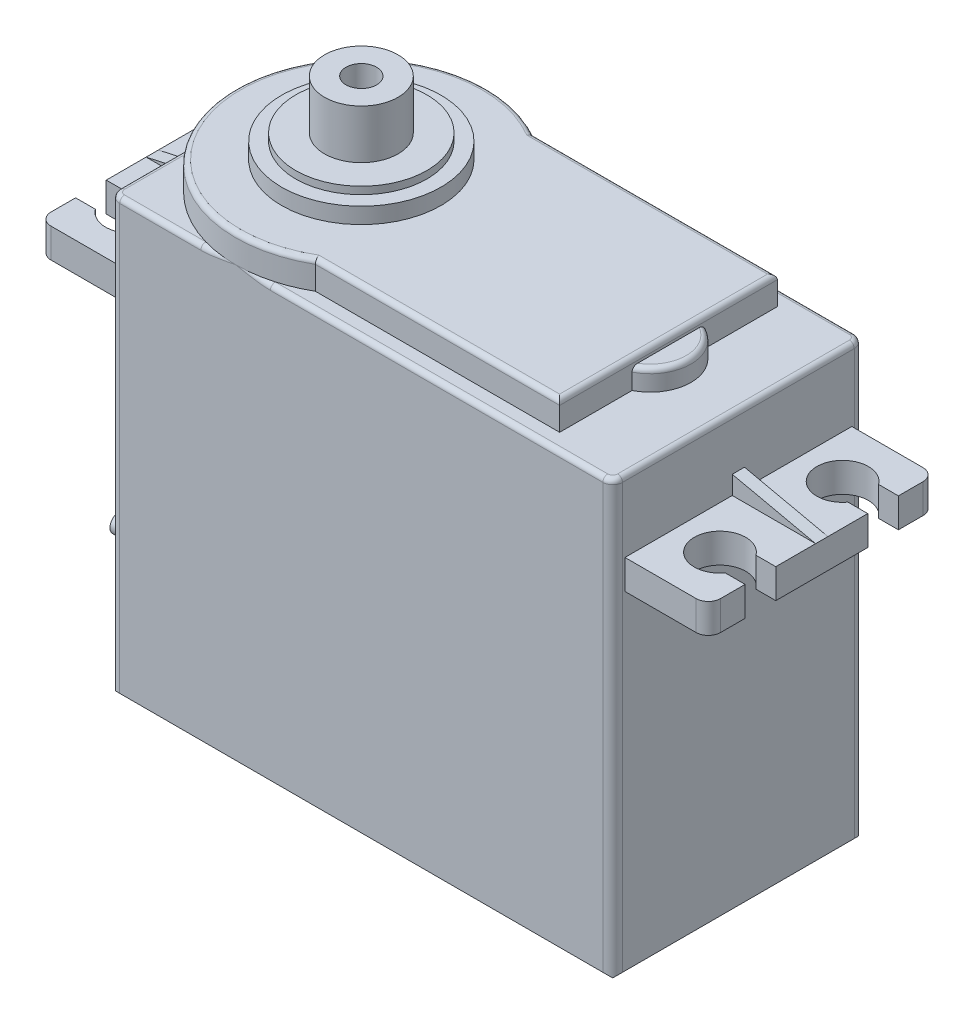
SolidWorks part; units mm, degrees
ref_plane "Front Plane" through (0, 0, 0) normal (0, 0, 1) x (1, 0, 0)
ref_plane "Top Plane" through (0, 0, 0) normal (0, 1, 0) x (1, 0, 0)
ref_plane "Right Plane" through (0, 0, 0) normal (1, 0, 0) x (0, 0, -1)
sketch "Sketch1" plane through (0, 0, 0) normal (0, 1, 0) x (1, 0, 0)
  line L1 (-20.5, -10.25) -> (20.5, -10.25)
  line L2 (-20.5, -10.25) -> (-20.5, 10.25)
  line L3 (-20.5, 10.25) -> (20.5, 10.25)
  line L4 (20.5, -10.25) -> (20.5, 10.25)
  line L5 (-20.5, -10.25) -> (20.5, 10.25) construction
  line L6 (-20.5, 10.25) -> (20.5, -10.25) construction
  point P0 (0, 0)
  dimension "D1" = 41
  dimension "D2" = 20.5
extrude "Boss-Extrude1" add sketch "Sketch1" along normal blind 37
sketch "Sketch2" plane through (0, 37, 0) normal (0, 1, 0) x (1, 0, 0)
  line L0 (-20.5, 10.25) -> (-20.5, -10.25) construction
  line L1 (20.5, -10.25) -> (20.5, 10.25) construction
  line L2 (-5.122, -8.875) -> (14.8, -8.875)
  line L4 (-5.122, 8.875) -> (14.8, 8.875)
  line L5 (14.8, -8.875) -> (14.8, -2.9672)
  line L9 (14.8, 2.9672) -> (14.8, 8.875)
  arc A0 (-5.122, 8.875) -> (-5.122, -8.875) centre (-10.25, 0) ccw
  arc A1 (14.8, -2.9672) -> (14.8, 2.9672) centre (13.3208, 0) ccw
  point P5 (4.4919, 0)
  dimension "D1" = 10.25
  dimension "D2" = 17.75
  dimension "D3" = 5.7
extrude "Boss-Extrude2" add sketch "Sketch2" along normal blind 2.3
sketch "Sketch3" plane through (0, 39.3, 0) normal (0, 1, 0) x (1, 0, 0)
  circle A0 centre (-10.25, 0) radius 6.5
  dimension "D1" = 13
extrude "Boss-Extrude3" add sketch "Sketch3" along normal blind 1.3
sketch "Sketch4" plane through (0, 40.6, 0) normal (0, 1, 0) x (1, 0, 0)
  circle A0 centre (-10.25, 0) radius 5.35
  dimension "D1" = 10.7
extrude "Boss-Extrude4" add sketch "Sketch4" along normal blind 0.6
sketch "Sketch5" plane through (0, 39.3, 0) normal (0, 1, 0) x (1, 0, 0)
  line L0 (14.8, 2.9672) -> (14.8, -2.9672)
  arc A0 (14.8, -2.9672) -> (14.8, 2.9672) centre (13.3208, 0) ccw construction
  arc A1 (14.8, -2.9672) -> (14.8, 2.9672) centre (13.3208, 0) ccw
extrude "Cut-Extrude1" cut sketch "Sketch5" against normal blind 0.6
sketch "Sketch6" plane through (0, 41.2, 0) normal (0, 1, 0) x (1, 0, 0)
  circle A0 centre (-10.25, 0) radius 3
  dimension "D1" = 6
extrude "Boss-Extrude5" add sketch "Sketch6" along normal blind 4
chamfer "Chamfer1" distance 2 angle 45 4 edges at (-20.5, 0, 0) (0, 0, -10.25) (20.5, 0, 0) (0, 0, 10.25)
fillet "Fillet2" radius 0.8 4 edges at (-20.5, 19.5, -10.25) (-20.5, 19.5, 10.25) (20.5, 19.5, -10.25) (20.5, 19.5, 10.25)
sketch "Sketch7" plane through (-20.5, 0, 0) normal (-1, 0, 0) x (0, 0, 1)
  line L1 (-9.25, 31.2) -> (9.25, 31.2)
  line L2 (-9.25, 31.2) -> (-9.25, 28.8)
  line L3 (-9.25, 28.8) -> (9.25, 28.8)
  line L4 (9.25, 31.2) -> (9.25, 28.8)
  line L6 (-9.45, 37) -> (0, 37) construction
  line L9 (-10.25, 37) -> (-10.25, 2) construction
  dimension "D1" = 5.8
  dimension "D2" = 2.4
  dimension "D3" = 18.5
  dimension "D4" = 1
extrude "Boss-Extrude6" add sketch "Sketch7" along normal blind 6.8
sketch "Sketch9" plane through (0, 31.2, 0) normal (0, 1, 0) x (1, 0, 0)
  line L0 (-27.3, -9.25) -> (-27.3, 9.25) construction
  line L3 (-25.6875, 6.25) -> (-27.3, 6.25)
  line L4 (-21.6, 3.75) -> (-22.3125, 3.75)
  line L5 (-21.6, 3.75) -> (-21.6, 6.25)
  line L6 (-21.6, 6.25) -> (-22.3125, 6.25)
  line L7 (-27.3, 3.75) -> (-27.3, 6.25)
  line L8 (-21.6, 3.75) -> (-24, 5) construction
  line L9 (-21.6, 6.25) -> (-24, 5) construction
  line L10 (-21.6, -6.25) -> (-27.3, -6.25)
  line L11 (-21.6, -6.25) -> (-21.6, -3.75)
  line L12 (-21.6, -3.75) -> (-27.3, -3.75)
  line L13 (-27.3, -6.25) -> (-27.3, -3.75)
  line L14 (-21.6, -6.25) -> (-24, -5) construction
  line L15 (-21.6, -3.75) -> (-24, -5) construction
  line L18 (-25.6875, 3.75) -> (-27.3, 3.75)
  arc A0 (-25.6875, 3.75) -> (-25.6875, 6.25) centre (-24, 5) ccw
  arc A1 (-25.6875, -6.25) -> (-25.6875, -3.75) centre (-24, -5) ccw
  line M4 (-27.3, 9.25) -> (-27.3, -9.25)
  dimension "D1" = 4.2
  dimension "D2" = 4.2
  dimension "D3" = 3.3
  dimension "D4" = 10
  dimension "D5" = 5
  dimension "D6" = 2.5
  dimension "D7" = 2.5
  dimension "D8" = 3.3
extrude "Cut-Extrude2" cut sketch "Sketch9" against normal blind 6.8 contours A0 L3 L18 M4 | L12 A1 | L10 A1 | L10 A1 L12 M4 region at (-24.5093, 31.2, -5) region at (-24.6644, 31.2, 5) region at (-24, 31.2, 3.4033) region at (-24, 31.2, 6.5967)
fillet "Fillet1" radius 1 2 edges at (-27.3, 30, 9.25) (-27.3, 30, -9.25)
sketch "Sketch10" plane through (0, 31.2, 0) normal (0, 1, 0) x (1, 0, 0)
  line L0 (-20.5, -9.25) -> (-20.5, 9.25) construction
  line L1 (-27.3, -0.5) -> (-20.5, -0.5)
  line L2 (-27.3, -0.5) -> (-27.3, 0.5)
  line L3 (-27.3, 0.5) -> (-20.5, 0.5)
  line L4 (-20.5, -0.5) -> (-20.5, 0.5)
  line L5 (-27.3, -0.5) -> (-20.5, 0.5) construction
  line L6 (-27.3, 0.5) -> (-20.5, -0.5) construction
  line L7 (-27.3, -3.75) -> (-27.3, 3.75) construction
  point P0 (-23.9, 0)
  dimension "D1" = 1
extrude "Boss-Extrude7" add sketch "Sketch10" along normal blind 1.5
sketch "Sketch11" plane through (0, 0, 0.5) normal (0, 0, 1) x (1, 0, 0)
  line L0 (-27.3, 31.2) -> (-20.5, 32.7)
  line L1 (-20.5, 32.7) -> (-27.3, 32.7)
  line L2 (-27.3, 32.7) -> (-27.3, 31.2)
extrude "Cut-Extrude3" cut sketch "Sketch11" against normal blind 1.5
ref_plane "Plane1" through (0, 0, 0) normal (-1, 0, 0) x (0, 0, 1)
mirror "Mirror2" about plane through (0, 0, 0) normal (-1, 0, 0) of "Cut-Extrude3", "Boss-Extrude7", "Fillet1", "Cut-Extrude2", "Boss-Extrude6"
sketch "Sketch12" plane through (0, 45.2, 0) normal (0, 1, 0) x (1, 0, 0)
  circle A0 centre (-10.25, 0) radius 1.25
  dimension "D1" = 2.5
extrude "Cut-Extrude4" cut sketch "Sketch12" against normal blind 4
fillet "Fillet5" radius 0.4 5 edges at (16.6363, 38.7, 0) (14.8, 39.3, 0) (4.839, 39.3, -8.875) (-20.5, 39.3, 0) (4.839, 39.3, 8.875)
fillet "Fillet7" radius 0.4 11 edges at (20.2657, 37, 10.0157) (4.725, 37, 10.25) (-14.975, 37, 10.25) (-20.2657, 37, 10.0157) (-20.5, 37, 4.725) (-20.5, 37, -4.725) (-20.2657, 37, -10.0157) (-14.975, 37, -10.25) (4.725, 37, -10.25) (20.2657, 37, -10.0157) (20.5, 37, 0)
sketch "Sketch13" plane through (-20.5, 0, 0) normal (-1, 0, 0) x (0, 0, 1)
  line L0 (8.25, 0) -> (-8.25, 0) construction
  line L1 (-3.5, 3.2) -> (3.5, 3.2)
  line L2 (-3.5, 3.2) -> (-3.5, 7.4)
  line L3 (-3.5, 7.4) -> (3.5, 7.4)
  line L4 (3.5, 3.2) -> (3.5, 7.4)
  line L5 (-3.5, 3.2) -> (3.5, 7.4) construction
  line L6 (-3.5, 7.4) -> (3.5, 3.2) construction
  point P0 (0, 5.3)
  dimension "D1" = 7
  dimension "D2" = 4.2
  dimension "D3" = 3.2
extrude "Boss-Extrude8" add sketch "Sketch13" along normal blind 1
sketch "Sketch14" plane through (-21.5, 0, 0) normal (-1, 0, 0) x (0, 0, 1)
  line L9 (3.15, 3.55) -> (3.15, 7.05)
  line L10 (3.15, 7.05) -> (-3.15, 7.05)
  line L11 (-3.15, 7.05) -> (-3.15, 3.55)
  line L12 (-3.15, 3.55) -> (3.15, 3.55)
  line L13 (3.15, 3.55) -> (3.15, 7.05)
  line L14 (3.15, 7.05) -> (-3.15, 7.05)
  line L15 (-3.15, 7.05) -> (-3.15, 3.55)
  line L16 (-3.15, 3.55) -> (3.15, 3.55)
  dimension "D1" = 0.35
extrude "Boss-Extrude9" add sketch "Sketch14" along normal blind 4 draft 5 contours L14 L15 L16 L13
sketch "Sketch15" plane through (-25.5, 0, 0) normal (-1, 0, 0) x (0, 0, 1)
  line L0 (-2.8, 3.9) -> (2.8, 3.9) construction
  circle A0 centre (-1.5, 5.3) radius 0.75
  circle A1 centre (0, 5.3) radius 0.75
  circle A2 centre (1.5, 5.3) radius 0.75
  dimension "D1" = 1.5
  dimension "D2" = 1.5
  dimension "D3" = 1.5
  dimension "D4" = 1.4
extrude "Boss-Extrude12" add sketch "Sketch15" along normal blind 3 separate body contours A0 | A1 | A2 region at (-25.5, 5.3, -1.5) region at (-25.5, 5.3, 1.5) region at (-25.5, 5.3, 0)
